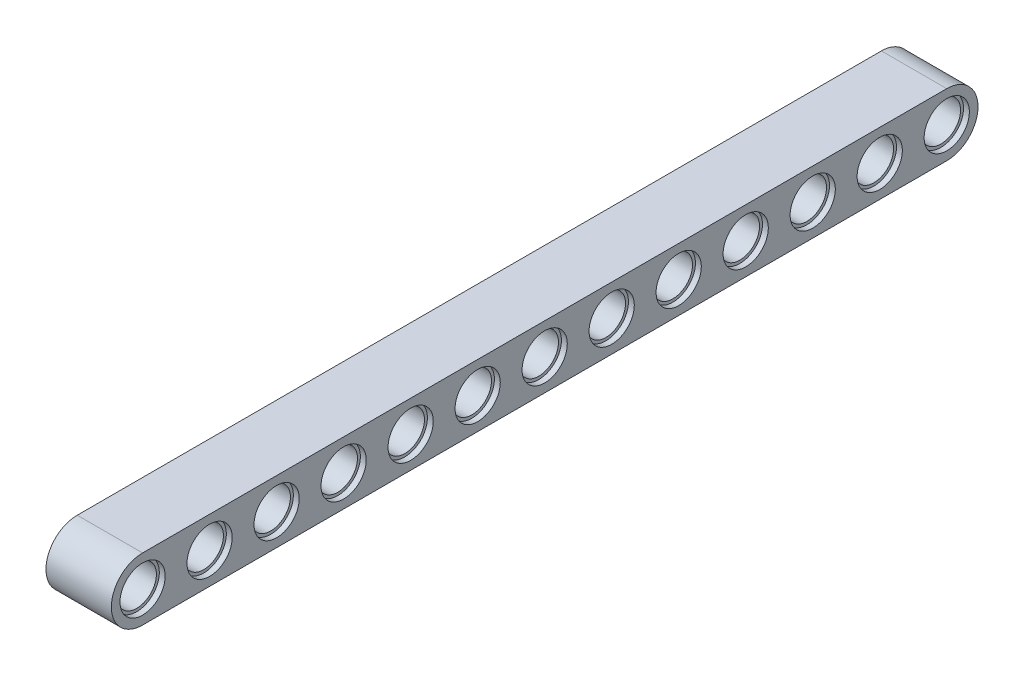
SolidWorks part; units mm, degrees
ref_plane "Front Plane" through (0, 0, 0) normal (0, 0, 1) x (1, 0, 0)
ref_plane "Top Plane" through (0, 0, 0) normal (0, 1, 0) x (1, 0, 0)
ref_plane "Right Plane" through (0, 0, 0) normal (1, 0, 0) x (0, 0, -1)
sketch "Sketch1" plane through (0, 0, 0) normal (1, 0, 0) x (0, 0, -1)
  line L0 (-48, 0) -> (48, 0) construction
  line L1 (-48, 3.73) -> (48, 3.73) construction
  line L2 (-48, 3.73) -> (-48, -3.73) construction
  line L3 (-48, -3.73) -> (48, -3.73) construction
  line L4 (48, 3.73) -> (48, -3.73) construction
  line L5 (-48, 3.73) -> (48, -3.73) construction
  line L6 (-48, -3.73) -> (48, 3.73) construction
  line L8 (-48, -3.73) -> (48, -3.73)
  line L10 (-48, 3.73) -> (48, 3.73)
  line L12 (-48, -3.73) -> (48, 3.73) construction
  line L13 (-48, 3.73) -> (48, -3.73) construction
  circle A0 centre (-48, 0) radius 2.35
  circle A1 centre (-40, 0) radius 2.35
  circle A2 centre (-32, 0) radius 2.35
  circle A3 centre (-24, 0) radius 2.35
  circle A4 centre (-16, 0) radius 2.35
  circle A5 centre (-8, 0) radius 2.35
  circle A6 centre (0, 0) radius 2.35
  circle A7 centre (8, 0) radius 2.35
  circle A8 centre (16, 0) radius 2.35
  circle A9 centre (24, 0) radius 2.35
  circle A10 centre (32, 0) radius 2.35
  circle A11 centre (40, 0) radius 2.35
  arc A12 (-48, 3.73) -> (-48, -3.73) centre (-48, 0) ccw
  arc A13 (48, -3.73) -> (48, 3.73) centre (48, 0) ccw
  circle A14 centre (48, 0) radius 2.35
  point P0 (0, 0)
  point P9 (0, 0)
  dimension "D3" = 4.7
  dimension "D5" = 8
  dimension "D6" = 4.7
  dimension "D1" = 96
  dimension "D2" = 7.46
  dimension "D4" = 12
extrude "Boss-Extrude1" add sketch "Sketch1" along normal blind 7.8
sketch "Sketch2" plane through (7.8, 0, 0) normal (1, 0, 0) x (0, 0, -1)
  circle A0 centre (-48, 0) radius 2.7
  circle A1 centre (-40, 0) radius 2.7
  circle A2 centre (-32, 0) radius 2.7
  circle A3 centre (-24, 0) radius 2.7
  circle A4 centre (-16, 0) radius 2.7
  circle A5 centre (-8, 0) radius 2.7
  circle A6 centre (0, 0) radius 2.7
  circle A7 centre (8, 0) radius 2.7
  circle A8 centre (16, 0) radius 2.7
  circle A9 centre (24, 0) radius 2.7
  circle A10 centre (32, 0) radius 2.7
  circle A11 centre (40, 0) radius 2.7
  circle A12 centre (48, 0) radius 2.7
  dimension "D1" = 5.4
  dimension "D2" = 13
  dimension "D3" = 8
extrude "Cut-Extrude1" cut sketch "Sketch2" against normal blind 0.7
sketch "Sketch3" plane through (0, 0, 0) normal (-1, 0, 0) x (0, 0, 1)
  line L0 (-48, 0) -> (-40, 0) construction
  circle A0 centre (-48, 0) radius 2.705
  circle A2 centre (-40, 0) radius 2.705
  circle A3 centre (-32, 0) radius 2.705
  circle A4 centre (-24, 0) radius 2.705
  circle A5 centre (-16, 0) radius 2.705
  circle A6 centre (-8, 0) radius 2.705
  circle A7 centre (0, 0) radius 2.705
  circle A8 centre (8, 0) radius 2.705
  circle A9 centre (16, 0) radius 2.705
  circle A10 centre (24, 0) radius 2.705
  circle A11 centre (32, 0) radius 2.705
  circle A12 centre (40, 0) radius 2.705
  circle A13 centre (48, 0) radius 2.705
  dimension "D1" = 5.41
  dimension "D3" = 8
  dimension "D2" = 13
extrude "Cut-Extrude2" cut sketch "Sketch3" against normal blind 0.7
